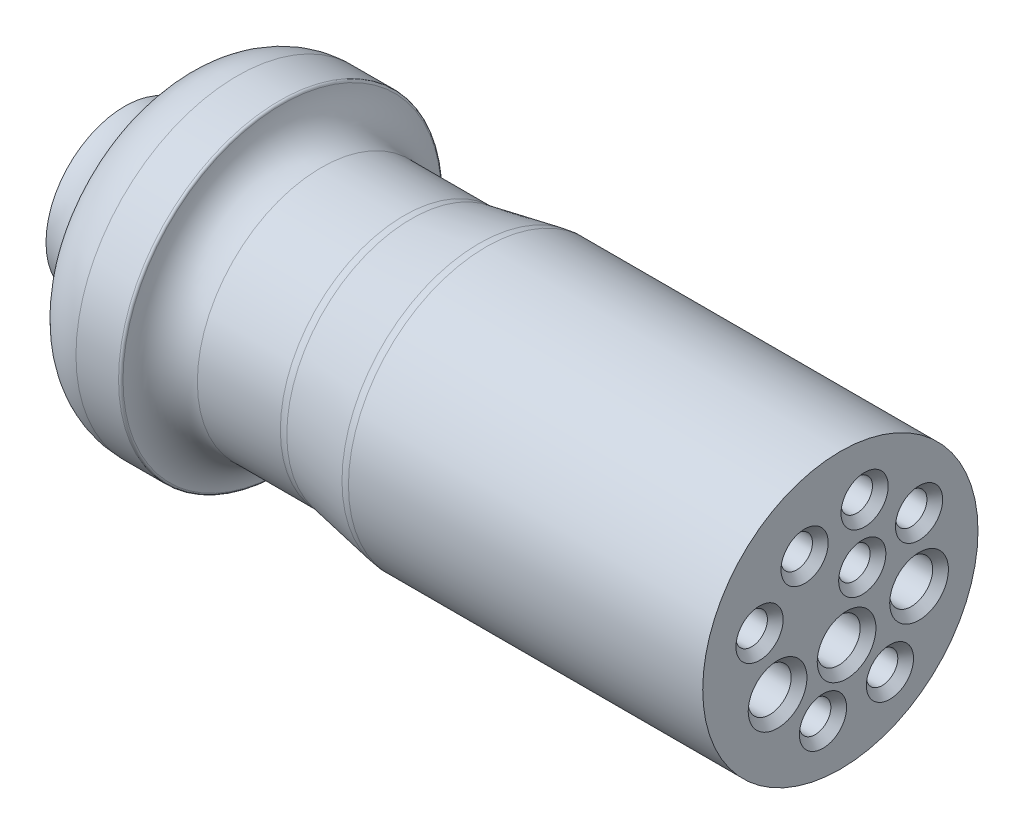
SolidWorks part; units mm, degrees
ref_plane "Front Plane" through (0, 0, 0) normal (0, 0, 1) x (1, 0, 0)
ref_plane "Top Plane" through (0, 0, 0) normal (0, 1, 0) x (1, 0, 0)
ref_plane "Right Plane" through (0, 0, 0) normal (1, 0, 0) x (0, 0, -1)
sketch "Sketch3" plane through (0, 0, 0) normal (0, 0, 1) x (1, 0, 0)
  line L0 (0, 0) -> (0, -50000) construction
  line L1 (0, 0) -> (50000, 0) construction
  line L2 (45.5, 0) -> (45.5, 17.5)
  line L3 (45.5, 17.5) -> (0, 17.5)
  line L4 (0, 17.5) -> (-9.5, 15.75)
  line L5 (-9.5, 15.75) -> (-25.5, 15.75)
  line L6 (-25.5, 15.75) -> (-25.5, 20.5)
  line L7 (-45.5, 0) -> (-45.5, 53.8042) construction
  line L8 (-25.5, 20.5) -> (-31.1909, 20.5)
  line L9 (-45.5, 10) -> (-36.3733, 10) construction
  line L10 (-45.5, 10) -> (-45.5, 0)
  line L11 (-45.5, 0) -> (45.5, 0)
  arc A0 (-45.5, 10) -> (-38.8224, 14.9) centre (-45.5, 17) ccw
  arc A1 (-38.8224, 14.9) -> (-31.1909, 20.5) centre (-31.1909, 12.5) cw
  dimension "D8" = 20
  dimension "D9" = 7
  dimension "D10" = 8
  dimension "D1" = 17.5
  dimension "D2" = 45.5
  dimension "D3" = 9.5
  dimension "D4" = 31.5
  dimension "D5" = 41
  dimension "D6" = 71
  dimension "D7" = 20
revolve "Revolve1" add sketch "Sketch3" angle 360 about L1
fillet "Fillet1" radius 5 1 edges at (-25.5, 0, 15.75)
fillet "Fillet2" radius 0.3 1 edges at (-25.5, 0, 20.5)
fillet "Fillet3" radius 5 2 edges at (0, 0, 17.5) (-9.5, 0, 15.75)
sketch "Sketch6" plane through (45.5, 0, 0) normal (1, 0, 0) x (0, 0, -1)
  line L0 (-16.3442, -6.4134) -> (3.8869, -6.4134) construction
  circle A0 centre (2.7838, 3.3454) radius 2.0006
  circle A1 centre (3.0831, 10.6474) radius 2.0006
  circle A2 centre (-4.5453, 8.2222) radius 2.0006
  circle A3 centre (-10.2777, 2.6222) radius 2.0006
  circle A4 centre (10.006, 5.7088) radius 2.0006
  circle A5 centre (-2.2083, -11.0914) radius 2.0006
  circle A6 centre (6.302, -9.9449) radius 2.0006
  circle A7 centre (10.006, -2.3606) radius 2.7332
  circle A8 centre (0.7901, -4.2126) radius 2.7332
  circle A9 centre (-7.9847, -5.2708) radius 2.7332
  point P6 (3.0831, 10.6474)
  point P9 (-4.5453, 8.2222)
  point P12 (-10.2777, 2.6222)
  point P15 (10.006, 5.7088)
  point P18 (-2.2083, -11.0914)
  point P21 (6.302, -9.9449)
  point P24 (9.7414, -2.2283)
  point P25 (10.006, -2.3606)
  point P28 (0.7901, -4.2126)
  point P31 (-7.9847, -5.2708)
extrude "Cut-Extrude1" cut sketch "Sketch6" against normal blind 21
chamfer "Chamfer1" distance 1 angle 45 10 edges at (45.5, -5.2708, 5.2516) (45.5, -11.0914, 0.2077) (45.5, -9.9449, -8.3026) (45.5, -4.2126, -3.5233) (45.5, 3.3454, -4.7844) (45.5, -2.3606, -12.7391) (45.5, 5.7088, -12.0066) (45.5, 10.6474, -5.0837) (45.5, 8.2222, 2.5447) (45.5, 2.6222, 8.2771)
